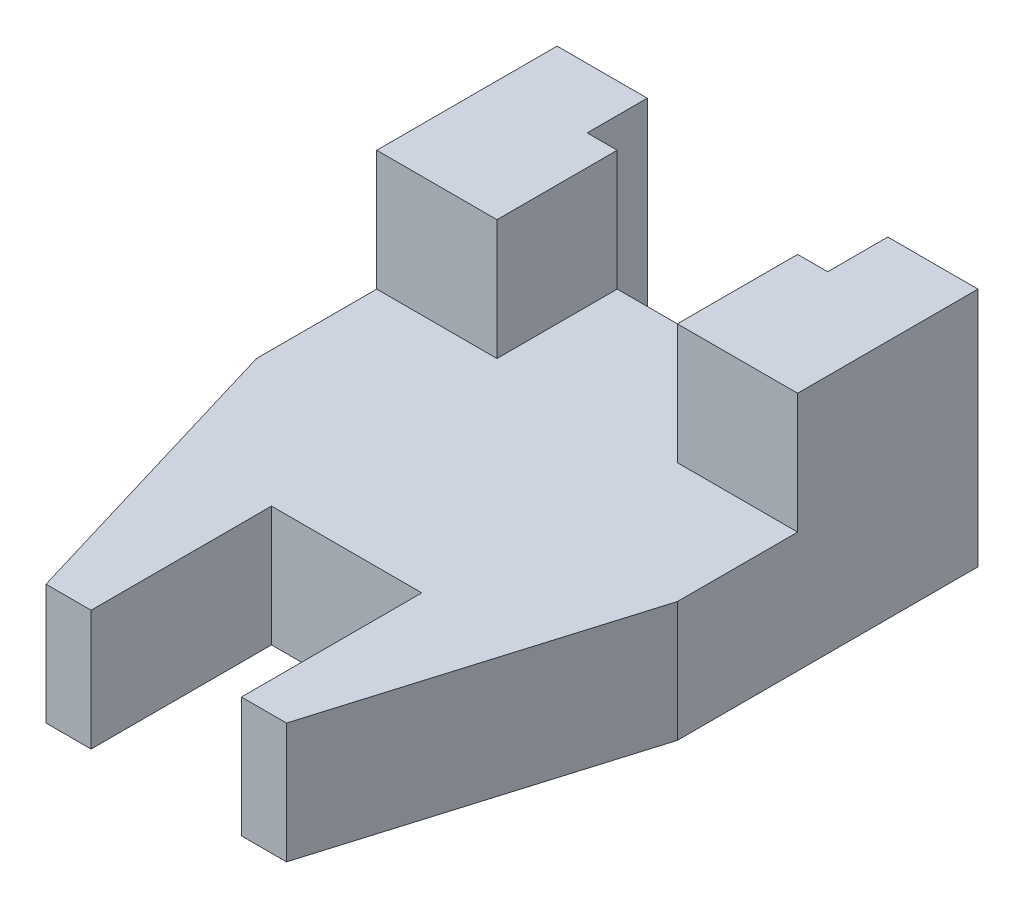
SolidWorks part; units mm, degrees
ref_plane "Front Plane" through (0, 0, 0) normal (0, 0, 1) x (1, 0, 0)
ref_plane "Top Plane" through (0, 0, 0) normal (0, 1, 0) x (1, 0, 0)
ref_plane "Right Plane" through (0, 0, 0) normal (1, 0, 0) x (0, 0, -1)
sketch "Sketch1" plane through (0, 0, 0) normal (0, 1, 0) x (1, 0, 0)
  line L0 (0, 0) -> (15, 0)
  line L1 (15, 0) -> (15, -10)
  line L2 (15, -10) -> (20, -10)
  line L3 (20, -10) -> (20, -30)
  line L4 (20, -30) -> (0, -30)
  line L5 (0, -30) -> (0, 0)
  line L6 (35, 18.4848) -> (35, -91.8182) construction
  line L7 (70, -30) -> (70, 0)
  line L8 (50, -30) -> (70, -30)
  line L9 (50, -10) -> (50, -30)
  line L10 (55, -10) -> (50, -10)
  line L11 (55, 0) -> (55, -10)
  line L12 (70, 0) -> (55, 0)
  line L13 (20, -10) -> (50, -10)
  line L14 (50, -30) -> (20, -30)
  line L15 (0, -30) -> (0, -50)
  line L16 (70, -30) -> (70, -50)
  line L17 (70, -50) -> (55, -100)
  line L18 (55, -100) -> (47.5, -100)
  line L19 (47.5, -100) -> (47.5, -70)
  line L20 (47.5, -70) -> (22.5, -70)
  line L21 (22.5, -100) -> (22.5, -70)
  line L22 (15, -100) -> (22.5, -100)
  line L23 (0, -50) -> (15, -100)
  point P22 (35, -70)
  dimension "D1" = 10
  dimension "D2" = 20
  dimension "D3" = 40
  dimension "D4" = 30
  dimension "D5" = 70
  dimension "D6" = 25
  dimension "D7" = 30
  dimension "D8" = 40
  dimension "D9" = 50
  dimension "D10" = 100
extrude "Boss-Extrude1" add sketch "Sketch1" along normal blind 20 contours L6 L14 L4 L15 L23 L22 L21 L20 | L14 L6 L20 L19 L18 L17 L16 L8 region at (17.7757, 0, 56.5441) region at (52.2243, 0, 56.5441)
extrude "Boss-Extrude2" add sketch "Sketch1<3>" along normal blind 40 contours L5 L4 L3 L2 L1 L0 | L7 L12 L11 L10 L9 L8 region at (9.3182, 0, 15.9091) region at (60.6818, 0, 15.9091)
sketch "Sketch1<3>" plane through (0, 0, 0) normal (0, 1, 0) x (1, 0, 0) same geometry as "Sketch1"
extrude "Boss-Extrude3" add sketch "Sketch1<4>" along normal blind 20 contours L6 L13 L3 L14 | L13 L6 L14 L9 region at (27.5, 0, 20) region at (42.5, 0, 20)
sketch "Sketch1<4>" plane through (0, 0, 0) normal (0, 1, 0) x (1, 0, 0) same geometry as "Sketch1"
